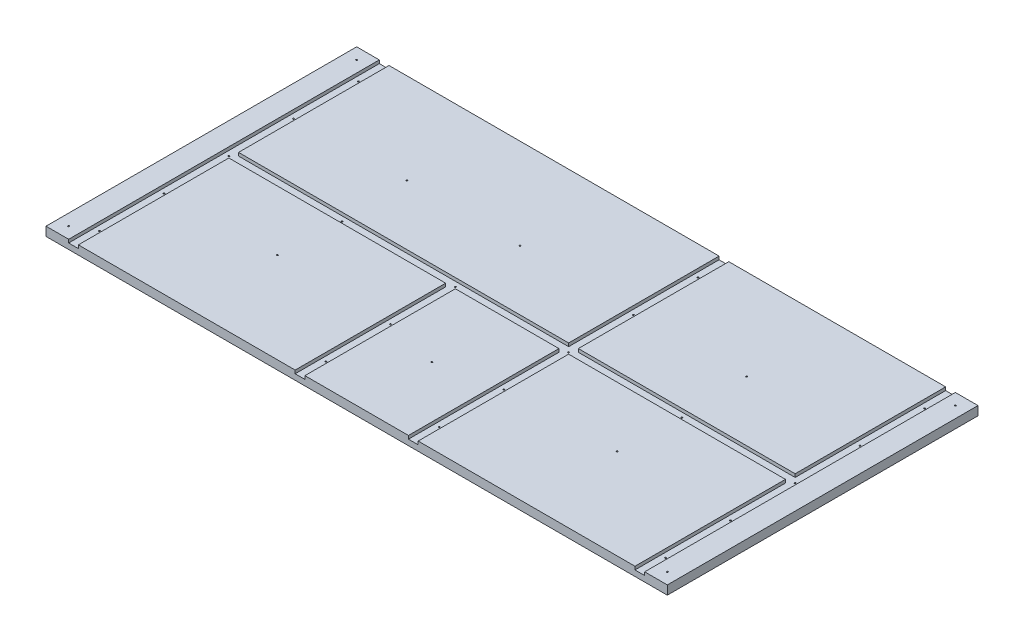
SolidWorks part; units mm, degrees
material "Cedar"
ref_plane "Front Plane" through (0, 0, 0) normal (0, 0, 1) x (1, 0, 0)
ref_plane "Top Plane" through (0, 0, 0) normal (0, 1, 0) x (1, 0, 0)
ref_plane "Right Plane" through (0, 0, 0) normal (1, 0, 0) x (0, 0, -1)
sketch "Sketch1" plane through (0, 0, 0) normal (0, 1, 0) x (1, 0, 0)
  line L1 (-609.6, -304.8) -> (609.6, -304.8)
  line L2 (-609.6, -304.8) -> (-609.6, 304.8)
  line L3 (-609.6, 304.8) -> (609.6, 304.8)
  line L4 (609.6, -304.8) -> (609.6, 304.8)
  line L5 (-609.6, -304.8) -> (609.6, 304.8) construction
  line L6 (-609.6, 304.8) -> (609.6, -304.8) construction
  point P0 (0, 0)
  dimension "D1" = 1219.2
  dimension "D2" = 609.6
extrude "Boss-Extrude1" add sketch "Sketch1" along normal blind 17.4752
sketch "Sketch2" plane through (0, 17.4752, 0) normal (0, 1, 0) x (1, 0, 0)
  line L0 (609.6, 304.8) -> (-609.6, 304.8) construction
  line L1 (-565.15, 304.8) -> (-546.1, 304.8)
  line L2 (-565.15, 304.8) -> (-565.15, -304.8)
  line L3 (-565.15, -304.8) -> (-546.1, -304.8)
  line L4 (-546.1, 304.8) -> (-546.1, 9.525)
  line L5 (-609.6, -304.8) -> (609.6, -304.8) construction
  line L7 (-546.1, 9.525) -> (101.6, 9.525)
  line L8 (-546.1, 9.525) -> (-546.1, -9.525) construction
  line L9 (-546.1, -9.525) -> (-120.65, -9.525)
  line L12 (565.15, 304.8) -> (546.1, 304.8)
  line L13 (565.15, 304.8) -> (565.15, -304.8)
  line L14 (565.15, -304.8) -> (546.1, -304.8)
  line L15 (546.1, 304.8) -> (546.1, 9.525)
  line L17 (-120.65, -9.525) -> (-101.6, -9.525) construction
  line L18 (-120.65, -9.525) -> (-120.65, -304.8)
  line L19 (-120.65, -304.8) -> (-101.6, -304.8)
  line L20 (-101.6, -9.525) -> (-101.6, -304.8)
  line L21 (-546.1, -9.525) -> (-546.1, -304.8)
  line L23 (101.6, -9.525) -> (101.6, -304.8)
  line L24 (101.6, -304.8) -> (120.65, -304.8)
  line L25 (120.65, -9.525) -> (120.65, -304.8)
  line L26 (-101.6, -9.525) -> (101.6, -9.525)
  line L27 (0, 0) -> (0, -9.525) construction
  line L28 (546.1, -9.525) -> (546.1, -304.8)
  line L29 (120.65, -9.525) -> (546.1, -9.525)
  line L30 (-565.15, 304.8) -> (-609.6, 304.8) construction
  line L31 (565.15, 304.8) -> (609.6, 304.8) construction
  line L32 (-609.6, 304.8) -> (-609.6, -304.8) construction
  line L33 (120.65, 9.525) -> (546.1, 9.525)
  line L35 (101.6, 9.525) -> (101.6, 304.8)
  line L36 (101.6, 304.8) -> (120.65, 304.8)
  line L37 (120.65, 9.525) -> (120.65, 304.8)
  line L38 (-546.1, 0) -> (-609.6, 0) construction
  dimension "D1" = 19.05
  dimension "D3" = 425.45
  dimension "D4" = 203.2
  dimension "D5" = 44.45
extrude "Cut-Extrude1" cut sketch "Sketch2" against normal blind 6.35
sketch "Sketch4" plane through (0, 11.1252, 0) normal (0, 1, 0) x (1, 0, 0)
  line L0 (-546.1, -9.525) -> (-546.1, 9.525) construction
  line L1 (-120.65, -9.525) -> (-101.6, -9.525) construction
  line L2 (101.6, -9.525) -> (120.65, -9.525) construction
  line L3 (101.6, 9.525) -> (120.65, 9.525) construction
  line L4 (120.65, 9.525) -> (120.65, 304.8) construction
  line L5 (120.65, 9.525) -> (120.65, 304.8) construction
  line L6 (-565.15, 304.8) -> (-546.1, 304.8) construction
  line L7 (565.15, 304.8) -> (546.1, 304.8) construction
  line L8 (-101.6, -304.8) -> (-120.65, -304.8) construction
  line L9 (120.65, -304.8) -> (101.6, -304.8) construction
  line L10 (120.65, 304.8) -> (101.6, 304.8) construction
  line L11 (120.65, 304.8) -> (101.6, 304.8) construction
  line L12 (-546.1, 0) -> (546.1, 0) construction
  line L13 (0, 0) -> (0, -157.1625) construction
  line L14 (546.1, 9.525) -> (546.1, -9.525) construction
  line L15 (-555.625, 304.8) -> (-555.625, -304.8) construction
  line L16 (-565.15, -304.8) -> (-546.1, -304.8) construction
  line L17 (-587.375, -282.575) -> (-587.375, -304.8) construction
  line L18 (-565.15, 304.8) -> (-609.6, 304.8) construction
  line L19 (-111.125, -304.8) -> (-111.125, -9.525) construction
  line L20 (111.125, -304.8) -> (111.125, -9.525) construction
  line L21 (111.125, 9.525) -> (111.125, 304.8) construction
  line L22 (555.625, 304.8) -> (555.625, -304.8) construction
  line L23 (546.1, -304.8) -> (565.15, -304.8) construction
  line L24 (-587.375, 282.575) -> (-587.375, 304.8) construction
  line L25 (-587.375, 282.575) -> (-609.6, 282.575) construction
  line L26 (-609.6, 304.8) -> (-609.6, -304.8) construction
  line L27 (-609.6, -304.8) -> (-565.15, -304.8) construction
  line L28 (587.375, 282.575) -> (609.6, 282.575) construction
  line L29 (609.6, -304.8) -> (609.6, 304.8) construction
  line L30 (0, -157.1625) -> (-101.6, -157.1625) construction
  line L31 (-101.6, -304.8) -> (-101.6, -9.525) construction
  circle A0 centre (-555.625, 254) radius 1.397
  circle A3 centre (111.125, 254) radius 1.397
  circle A5 centre (555.625, 254) radius 1.397
  circle A6 centre (-333.375, 127) radius 1.397
  circle A7 centre (-111.125, 127) radius 1.397
  circle A8 centre (111.125, 127) radius 1.397
  circle A9 centre (333.375, 127) radius 1.397
  circle A10 centre (555.625, 127) radius 1.397
  circle A11 centre (-333.375, 0) radius 1.397
  circle A12 centre (-111.125, 0) radius 1.397
  circle A13 centre (111.125, 0) radius 1.397
  circle A14 centre (333.375, 0) radius 1.397
  circle A15 centre (555.625, 0) radius 1.397
  circle A16 centre (-333.375, -127) radius 1.397
  circle A17 centre (-111.125, -127) radius 1.397
  circle A18 centre (111.125, -127) radius 1.397
  circle A19 centre (333.375, -127) radius 1.397
  circle A20 centre (555.625, -127) radius 1.397
  circle A22 centre (-111.125, -254) radius 1.397
  circle A23 centre (111.125, -254) radius 1.397
  circle A25 centre (555.625, -254) radius 1.397
  circle A26 centre (-555.625, 127) radius 1.397
  circle A27 centre (-555.625, 0) radius 1.397
  circle A28 centre (-555.625, -127) radius 1.397
  circle A29 centre (-555.625, -254) radius 1.397
  circle A30 centre (-587.375, 282.575) radius 1.397
  circle A31 centre (587.375, 282.575) radius 1.397
  circle A32 centre (587.375, -282.575) radius 1.397
  circle A33 centre (-587.375, -282.575) radius 1.397
  circle A34 centre (-333.375, -254) radius 1.397 [skipped]
  circle A35 centre (333.375, -254) radius 1.397 [skipped]
  circle A36 centre (-333.375, 254) radius 1.397 [skipped]
  circle A37 centre (-111.125, 254) radius 1.397 [skipped]
  circle A38 centre (333.375, 254) radius 1.397 [skipped]
  circle A39 centre (0, -157.1625) radius 1.397
  point P27 (555.625, 304.8)
  point P28 (111.125, 9.525)
  point P29 (111.125, -9.525)
  point P30 (-111.125, -9.525)
  point P31 (-546.1, 0)
  point P32 (-555.625, 304.8)
  point P37 (-111.125, -304.8)
  point P42 (111.125, -304.8)
  point P48 (111.125, 304.8)
  dimension "D1" = 2.794
  dimension "D4" = 127
  dimension "D2" = 6
  dimension "D3" = 5
  dimension "D5" = 2
  dimension "D6" = 2
sketch "Sketch5" plane through (0, 11.1252, 0) normal (0, 1, 0) x (1, 0, 0)
  line L0 (-101.6, -9.525) -> (101.6, -9.525) construction
  point P0 (0, -9.525)
extrude "Cut-Extrude2" cut sketch "Sketch4" against normal through all both and the other way through all
